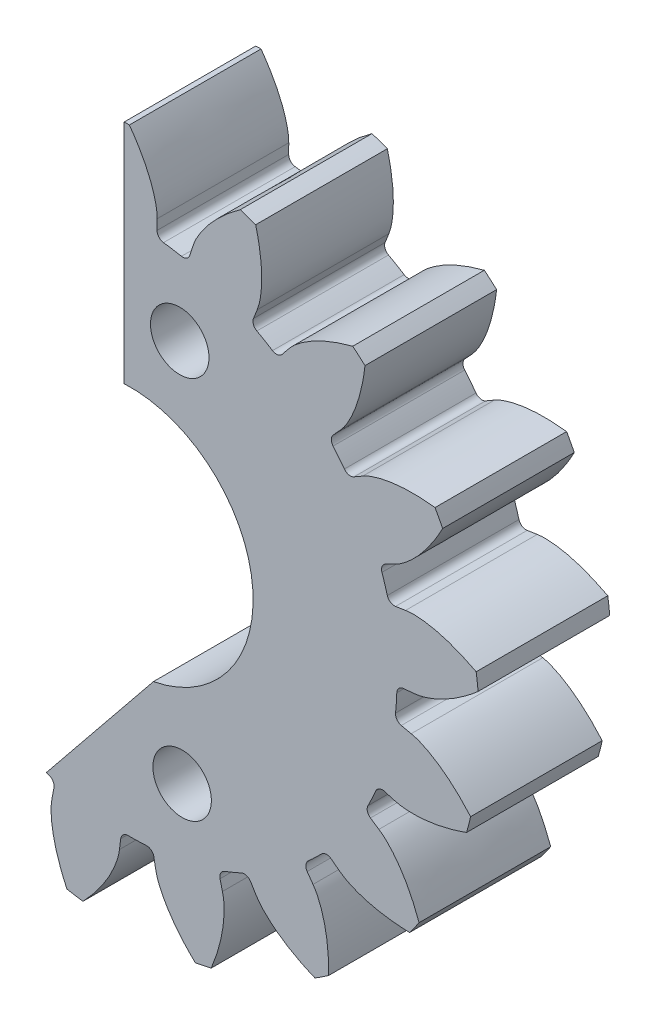
SolidWorks part; units mm, degrees
ref_plane "Front" through (0, 0, 0) normal (0, 0, 1) x (1, 0, 0)
ref_plane "Top" through (0, 0, 0) normal (0, 1, 0) x (1, 0, 0)
ref_plane "Right" through (0, 0, 0) normal (1, 0, 0) x (0, 0, -1)
sketch "Sketch1" plane through (0, 0, 0) normal (0, 0, 1) x (1, 0, 0)
  line L68 (2.1427, 9.4464) -> (2.0368, 9.1165)
  line L69 (0.916, 9.2963) -> (0.9185, 9.6427)
  line L70 (-1.4144, 9.5825) -> (-1.394, 9.2367)
  line L71 (-2.504, 8.9994) -> (-2.6268, 9.3234)
  line L72 (-4.7805, 8.4245) -> (-4.6366, 8.1093)
  line L73 (-5.5859, 7.4871) -> (-5.8174, 7.7449)
  line L74 (-7.501, 6.1287) -> (-7.2529, 5.8868)
  line L75 (-7.9134, 4.9637) -> (-8.2224, 5.1204)
  line L76 (-9.2084, 3.0052) -> (-8.8897, 2.8692)
  line L77 (-9.1721, 1.7699) -> (-9.5168, 1.8043)
  line L78 (-9.6722, -0.5242) -> (-9.3259, -0.5358)
  line L79 (-9.1921, -1.663) -> (-9.526, -1.7554)
  line L80 (-8.8296, -3.9828) -> (-8.5026, -3.8686)
  line L81 (-7.9706, -4.8713) -> (-8.2486, -5.078)
  line L82 (-6.7946, -6.9035) -> (-6.5309, -6.6788)
  line L83 (-5.6727, -7.4216) -> (-5.8572, -7.7148)
  line L84 (-3.842, -8.8918) -> (-3.6772, -8.587)
  line L85 (-2.6086, -8.9696) -> (-2.6747, -9.3097)
  line L86 (-0.3704, -9.6793) -> (-0.3269, -9.3356)
  line L87 (0.8078, -9.3063) -> (0.8689, -9.6473)
  line L88 (3.1511, -9.1595) -> (3.0675, -8.8232)
  line L89 (4.115, -8.3861) -> (4.2953, -8.6819)
  line L90 (6.2471, -7.4026) -> (6.0477, -7.1193)
  line L91 (6.8665, -6.3332) -> (7.1415, -6.544)
  line L92 (8.4994, -4.646) -> (8.2111, -4.4539)
  line L93 (8.6907, -3.4251) -> (9.0232, -3.5223)
  line L94 (9.6038, -1.2619) -> (9.2656, -1.1869)
  line L95 (9.3411, -0.0544) -> (9.6863, -0.0249)
  line L96 (9.4111, 2.2926) -> (9.0686, 2.2404)
  line L97 (8.73, 3.3237) -> (9.0412, 3.4759)
  line L98 (7.9475, 5.5374) -> (7.6469, 5.365)
  line L99 (6.9398, 6.2529) -> (7.1751, 6.5072)
  line L100 (5.4104, 8.0345) -> (5.1925, 7.7651)
  line L101 (4.2123, 8.3376) -> (4.3399, 8.6597)
  circle A0 centre (0, 0) radius 1.5
  arc A136 (4.2867, 11.1494) -> (3.764, 11.3366) centre (0, 0) ccw
  arc A137 (1.7491, 8.9466) -> (2.0368, 9.1165) centre (1.7973, 9.1934) ccw
  arc A138 (1.7491, 8.9466) -> (1.1361, 9.0449) centre (0, 0) ccw
  arc A139 (0.916, 9.2963) -> (1.1361, 9.0449) centre (1.1675, 9.2944) ccw
  arc A140 (-0.0304, 11.945) -> (-0.5854, 11.9307) centre (0, 0) ccw
  arc A141 (-1.6009, 8.9743) -> (-1.394, 9.2367) centre (-1.6451, 9.2219) ccw
  arc A142 (-1.6009, 8.9743) -> (-2.208, 8.8445) centre (0, 0) ccw
  arc A143 (-2.504, 8.9994) -> (-2.208, 8.8445) centre (-2.2689, 9.0885) ccw
  arc A144 (-4.3434, 11.1274) -> (-4.8558, 10.9136) centre (0, 0) ccw
  arc A145 (-4.7347, 7.79) -> (-4.6366, 8.1093) centre (-4.8653, 8.0049) ccw
  arc A146 (-4.7347, 7.79) -> (-5.2539, 7.4497) centre (0, 0) ccw
  arc A147 (-5.5859, 7.4871) -> (-5.2539, 7.4497) centre (-5.3988, 7.6552) ccw
  arc A148 (-8.0698, 8.807) -> (-8.4703, 8.4225) centre (0, 0) ccw
  arc A149 (-7.229, 5.5536) -> (-7.2529, 5.8868) centre (-7.4285, 5.7068) ccw
  arc A150 (-7.229, 5.5536) -> (-7.5902, 5.0487) centre (0, 0) ccw
  arc A151 (-7.9134, 4.9637) -> (-7.5902, 5.0487) centre (-7.7996, 5.188) ccw
  arc A152 (-10.7063, 5.2971) -> (-10.9409, 4.7939) centre (0, 0) ccw
  arc A153 (-8.7471, 2.5671) -> (-8.8897, 2.8692) centre (-8.9884, 2.6379) ccw
  arc A154 (-8.7471, 2.5671) -> (-8.9015, 1.9659) centre (0, 0) ccw
  arc A155 (-9.1721, 1.7699) -> (-8.9015, 1.9659) centre (-9.147, 2.0201) ccw
  arc A156 (-11.8969, 1.0719) -> (-11.9338, 0.5179) centre (0, 0) ccw
  arc A157 (-9.0837, -0.766) -> (-9.3259, -0.5358) centre (-9.3343, -0.7872) ccw
  arc A158 (-9.0837, -0.766) -> (-9.0105, -1.3825) centre (0, 0) ccw
  arc A159 (-9.1921, -1.663) -> (-9.0105, -1.3825) centre (-9.2591, -1.4206) ccw
  arc A160 (-11.4807, -3.2982) -> (-11.3151, -3.8281) centre (0, 0) ccw
  arc A161 (-8.1936, -3.9957) -> (-8.5026, -3.8686) centre (-8.4196, -4.106) ccw
  arc A162 (-8.1936, -3.9957) -> (-7.9027, -4.5441) centre (0, 0) ccw
  arc A163 (-7.9706, -4.8713) -> (-7.9027, -4.5441) centre (-8.1207, -4.6695) ccw
  arc A164 (-9.514, -7.2228) -> (-9.1681, -7.6571) centre (0, 0) ccw
  arc A165 (-6.1969, -6.6858) -> (-6.5309, -6.6788) centre (-6.3678, -6.8702) ccw
  arc A166 (-6.1969, -6.6858) -> (-5.7275, -7.092) centre (0, 0) ccw
  arc A167 (-5.6727, -7.4216) -> (-5.7275, -7.092) centre (-5.8855, -7.2877) ccw
  arc A168 (-6.2624, -10.1719) -> (-5.783, -10.4519) centre (0, 0) ccw
  arc A169 (-3.3632, -8.4729) -> (-3.6772, -8.587) centre (-3.456, -8.7066) ccw
  arc A170 (-3.3632, -8.4729) -> (-2.7788, -8.6821) centre (0, 0) ccw
  arc A171 (-2.6086, -8.9696) -> (-2.7788, -8.6821) centre (-2.8554, -8.9216) ccw
  arc A172 (-2.165, -11.7472) -> (-1.6168, -11.8352) centre (0, 0) ccw
  arc A173 (-0.0754, -9.1157) -> (-0.3269, -9.3356) centre (-0.0774, -9.3671) ccw
  arc A174 (-0.0754, -9.1157) -> (0.5452, -9.0997) centre (0, 0) ccw
  arc A175 (0.8078, -9.3063) -> (0.5452, -9.0997) centre (0.5602, -9.3507) ccw
  arc A176 (2.2248, -11.7361) -> (2.7677, -11.62) centre (0, 0) ccw
  arc A177 (3.2227, -8.5273) -> (3.0675, -8.8232) centre (3.3116, -8.7626) ccw
  arc A178 (3.2227, -8.5273) -> (3.7956, -8.2882) centre (0, 0) ccw
  arc A179 (4.115, -8.3861) -> (3.7956, -8.2882) centre (3.9003, -8.5169) ccw
  arc A180 (6.3141, -10.1399) -> (6.7785, -9.8355) centre (0, 0) ccw
  arc A181 (6.0855, -6.7873) -> (6.0477, -7.1193) centre (6.2534, -6.9746) ccw
  arc A182 (6.0855, -6.7873) -> (6.5333, -6.3574) centre (0, 0) ccw
  arc A183 (6.8665, -6.3332) -> (6.5333, -6.3574) centre (6.7135, -6.5328) ccw
  arc A184 (9.5507, -7.1742) -> (9.8737, -6.7227) centre (0, 0) ccw
  arc A185 (8.1264, -4.1307) -> (8.2111, -4.4539) centre (8.3506, -4.2446) ccw
  arc A186 (8.1264, -4.1307) -> (8.3887, -3.568) centre (0, 0) ccw
  arc A187 (8.6907, -3.4251) -> (8.3887, -3.568) centre (8.6201, -3.6665) ccw
  arc A188 (11.4974, -3.2397) -> (11.6355, -2.7019) centre (0, 0) ccw
  arc A189 (9.0698, -0.9161) -> (9.2656, -1.1869) centre (9.32, -0.9414) ccw
  arc A190 (9.0698, -0.9161) -> (9.1112, -0.2967) centre (0, 0) ccw
  arc A191 (9.3411, -0.0544) -> (9.1112, -0.2967) centre (9.3625, -0.3049) ccw
  arc A192 (11.8913, 1.1324) -> (11.8258, 1.6838) centre (0, 0) ccw
  arc A193 (8.7883, 2.4221) -> (9.0686, 2.2404) centre (9.0307, 2.489) ccw
  arc A194 (8.7883, 2.4221) -> (8.6031, 3.0146) centre (0, 0) ccw
  arc A195 (8.73, 3.3237) -> (8.6031, 3.0146) centre (8.8404, 3.0978) ccw
  arc A196 (10.6792, 5.3516) -> (10.419, 5.842) centre (0, 0) ccw
  arc A197 (7.3199, 5.4333) -> (7.6469, 5.365) centre (7.5218, 5.5832) ccw
  arc A198 (7.3199, 5.4333) -> (6.9331, 5.9189) centre (0, 0) ccw
  arc A199 (6.9398, 6.2529) -> (6.9331, 5.9189) centre (7.1244, 6.0821) ccw
  arc A200 (8.0248, 8.848) -> (7.605, 9.2113) centre (0, 0) ccw
  arc A201 (4.8629, 7.7106) -> (5.1925, 7.7651) centre (4.997, 7.9233) ccw
  arc A202 (4.8629, 7.7106) -> (4.3268, 8.0237) centre (0, 0) ccw
  arc A203 (4.2123, 8.3376) -> (4.3268, 8.0237) centre (4.4462, 8.245) ccw
  spline S68 degree 3 poles (3.764, 11.3366) (3.2587, 10.9714) (2.6231, 10.3935) (2.2067, 9.6531) (2.1427, 9.4464) knots -0.008485 -0.008485 -0.008485 -0.008485 0.741457 1 1 1 1
  spline S69 degree 3 poles (0.9185, 9.6427) (0.9201, 9.8535) (0.7567, 10.6863) (0.3366, 11.435) (-0.0304, 11.945) knots 0 0 0 0 0.250058 1 1 1 1
  spline S70 degree 3 poles (-0.5854, 11.9307) (-0.9247, 11.4077) (-1.3085, 10.6392) (-1.4294, 9.7984) (-1.4144, 9.5825) knots -0.008485 -0.008485 -0.008485 -0.008485 0.741457 1 1 1 1
  spline S71 degree 3 poles (-2.6268, 9.3234) (-2.7015, 9.5204) (-3.1547, 10.238) (-3.8169, 10.7844) (-4.3434, 11.1274) knots 0 0 0 0 0.250058 1 1 1 1
  spline S72 degree 3 poles (-4.8558, 10.9136) (-4.9832, 10.3033) (-5.0635, 9.4481) (-4.8725, 8.6204) (-4.7805, 8.4245) knots -0.008485 -0.008485 -0.008485 -0.008485 0.741457 1 1 1 1
  spline S73 degree 3 poles (-5.8174, 7.7449) (-5.9583, 7.9016) (-6.64, 8.4071) (-7.455, 8.6773) (-8.0698, 8.807) knots 0 0 0 0 0.250058 1 1 1 1
  spline S74 degree 3 poles (-8.4703, 8.4225) (-8.3687, 7.8074) (-8.1346, 6.9809) (-7.6575, 6.2781) (-7.501, 6.1287) knots -0.008485 -0.008485 -0.008485 -0.008485 0.741457 1 1 1 1
  spline S75 degree 3 poles (-8.2224, 5.1204) (-8.4103, 5.2157) (-9.2286, 5.4407) (-10.0862, 5.3983) (-10.7063, 5.2971) knots 0 0 0 0 0.250058 1 1 1 1
  spline S76 degree 3 poles (-10.9409, 4.7939) (-10.624, 4.2571) (-10.1071, 3.5709) (-9.4083, 3.088) (-9.2084, 3.0052) knots -0.008485 -0.008485 -0.008485 -0.008485 0.741457 1 1 1 1
  spline S77 degree 3 poles (-9.5168, 1.8043) (-9.7265, 1.8253) (-10.5708, 1.7395) (-11.3552, 1.3902) (-11.8969, 1.0719) knots 0 0 0 0 0.250058 1 1 1 1
  spline S78 degree 3 poles (-11.9338, 0.5179) (-11.4444, 0.1318) (-10.7145, -0.3213) (-9.8885, -0.5192) (-9.6722, -0.5242) knots -0.008485 -0.008485 -0.008485 -0.008485 0.741457 1 1 1 1
  spline S79 degree 3 poles (-9.526, -1.7554) (-9.7291, -1.8116) (-10.4854, -2.1966) (-11.0906, -2.8056) (-11.4807, -3.2982) knots 0 0 0 0 0.250058 1 1 1 1
  spline S80 degree 3 poles (-11.3151, -3.8281) (-10.7192, -4.0113) (-9.875, -4.1701) (-9.0332, -4.0563) (-8.8296, -3.9828) knots -0.008485 -0.008485 -0.008485 -0.008485 0.741457 1 1 1 1
  spline S81 degree 3 poles (-8.2486, -5.078) (-8.4177, -5.2038) (-8.9839, -5.836) (-9.3281, -6.6225) (-9.514, -7.2228) knots 0 0 0 0 0.250058 1 1 1 1
  spline S82 degree 3 poles (-9.1681, -7.6571) (-8.5463, -7.6126) (-7.7017, -7.4558) (-6.9579, -7.0456) (-6.7946, -6.9035) knots -0.008485 -0.008485 -0.008485 -0.008485 0.741457 1 1 1 1
  spline S83 degree 3 poles (-5.8572, -7.7148) (-5.9694, -7.8932) (-6.269, -8.6873) (-6.3059, -9.545) (-6.2624, -10.1719) knots 0 0 0 0 0.250058 1 1 1 1
  spline S84 degree 3 poles (-5.783, -10.4519) (-5.2192, -10.1859) (-4.4883, -9.7345) (-3.9429, -9.0833) (-3.842, -8.8918) knots -0.008485 -0.008485 -0.008485 -0.008485 0.741457 1 1 1 1
  spline S85 degree 3 poles (-2.6747, -9.3097) (-2.715, -9.5166) (-2.7074, -10.3653) (-2.432, -11.1784) (-2.165, -11.7472) knots 0 0 0 0 0.250058 1 1 1 1
  spline S86 degree 3 poles (-1.6168, -11.8352) (-1.1872, -11.3834) (-0.6687, -10.6985) (-0.3954, -9.8942) (-0.3704, -9.6793) knots -0.008485 -0.008485 -0.008485 -0.008485 0.741457 1 1 1 1
  spline S87 degree 3 poles (0.8689, -9.6473) (0.9062, -9.8547) (1.2197, -10.6434) (1.7703, -11.3021) (2.2248, -11.7361) knots 0 0 0 0 0.250058 1 1 1 1
  spline S88 degree 3 poles (2.7677, -11.62) (3.0051, -11.0436) (3.2412, -10.2176) (3.2055, -9.3689) (3.1511, -9.1595) knots -0.008485 -0.008485 -0.008485 -0.008485 0.741457 1 1 1 1
  spline S89 degree 3 poles (4.2953, -8.6819) (4.4049, -8.8619) (4.9822, -9.484) (5.7336, -9.8994) (6.3141, -10.1399) knots 0 0 0 0 0.250058 1 1 1 1
  spline S90 degree 3 poles (6.7785, -9.8355) (6.7916, -9.2122) (6.7134, -8.3568) (6.3735, -7.5783) (6.2471, -7.4026) knots -0.008485 -0.008485 -0.008485 -0.008485 0.741457 1 1 1 1
  spline S91 degree 3 poles (7.1415, -6.544) (7.3088, -6.6723) (8.0718, -7.0438) (8.9225, -7.1597) (9.5507, -7.1742) knots 0 0 0 0 0.250058 1 1 1 1
  spline S92 degree 3 poles (9.8737, -6.7227) (9.6608, -6.1367) (9.2788, -5.3673) (8.6807, -4.7642) (8.4994, -4.646) knots -0.008485 -0.008485 -0.008485 -0.008485 0.741457 1 1 1 1
  spline S93 degree 3 poles (9.0232, -3.5223) (9.2255, -3.5815) (10.0712, -3.6523) (10.9064, -3.4531) (11.4974, -3.2397) knots 0 0 0 0 0.250058 1 1 1 1
  spline S94 degree 3 poles (11.6355, -2.7019) (11.2253, -2.2324) (10.5911, -1.653) (9.8155, -1.3066) (9.6038, -1.2619) knots -0.008485 -0.008485 -0.008485 -0.008485 0.741457 1 1 1 1
  spline S95 degree 3 poles (9.6863, -0.0249) (9.8963, -0.007) (10.7105, 0.2325) (11.4173, 0.7199) (11.8913, 1.1324) knots 0 0 0 0 0.250058 1 1 1 1
  spline S96 degree 3 poles (11.8258, 1.6838) (11.2737, 1.9734) (10.4731, 2.2846) (9.6247, 2.3274) (9.4111, 2.2926) knots -0.008485 -0.008485 -0.008485 -0.008485 0.741457 1 1 1 1
  spline S97 degree 3 poles (9.0412, 3.4759) (9.2306, 3.5684) (9.9033, 4.0859) (10.3862, 4.7957) (10.6792, 5.3516) knots 0 0 0 0 0.250058 1 1 1 1
  spline S98 degree 3 poles (10.419, 5.842) (9.7996, 5.9126) (8.9406, 5.9136) (8.134, 5.6471) (7.9475, 5.5374) knots -0.008485 -0.008485 -0.008485 -0.008485 0.741457 1 1 1 1
  spline S99 degree 3 poles (7.1751, 6.5072) (7.3182, 6.6619) (7.7585, 7.3874) (7.9524, 8.2238) (8.0248, 8.848) knots 0 0 0 0 0.250058 1 1 1 1
  spline S100 degree 3 poles (7.605, 9.2113) (7.002, 9.0534) (6.2006, 8.744) (5.5448, 8.2041) (5.4104, 8.0345) knots -0.008485 -0.008485 -0.008485 -0.008485 0.741457 1 1 1 1
  spline S101 degree 3 poles (4.3399, 8.6597) (4.4174, 8.8557) (4.566, 9.6913) (4.4446, 10.5412) (4.2867, 11.1494) knots 0 0 0 0 0.250058 1 1 1 1
  dimension "D1" = 3
extrude "Boss-Extrude1" add sketch "Sketch1" along normal blind 4.5
sketch "Sketch3" plane through (0, 0, 4.5) normal (0, 0, 1) x (1, 0, 0)
  line L0 (0, 0) -> (-24.6444, 0)
sketch "Sketch4" plane through (0, 0, 0) normal (0, 0, -1) x (-1, 0, 0)
  line L0 (12.8632, 15.1898) -> (0.2099, 15.1898)
  line L1 (3.0728, -8.5825) -> (3.0728, -14.2917) construction
  line L2 (3.0728, -14.2917) -> (12.6632, -14.2917) construction
  line L4 (3.0728, -8.5825) -> (-0.6826, -3.9413) construction
  line L5 (12.6632, -14.2917) -> (12.6632, 14.9898) construction
  line L6 (12.6632, 14.9898) -> (0.4099, 14.9898) construction
  line L7 (0.2099, 15.1898) -> (0.2099, 4.1947)
  line L8 (2.8728, -8.6533) -> (-0.7915, -4.1248)
  line L9 (2.8728, -8.6533) -> (2.8728, -14.4917)
  line L10 (2.8728, -14.4917) -> (12.8632, -14.4917)
  line L11 (12.8632, -14.4917) -> (12.8632, 15.1898)
  line L22 (0.4099, 14.9898) -> (0.4099, 3.9789) construction
  arc A0 (0.2099, 4.1947) -> (-0.7915, -4.1248) centre (0, 0) ccw
  arc A3 (0.4099, 3.9789) -> (-0.6826, -3.9413) centre (0, 0) ccw construction
  dimension "D1" = 0.2
extrude "Cut-Extrude1" cut sketch "Sketch4" against normal through all
sketch "Sketch5" plane through (0, 0, 4.5) normal (0, 0, 1) x (1, 0, 0)
  line L1 (-0.2099, 11.9432) -> (-0.2099, 4.1947) construction
  circle A2 centre (1.6901, 6.4124) radius 1
  circle A3 centre (1.7728, -6.6584) radius 1
  dimension "D1" = 2
  dimension "D2" = 1.9
extrude "Cut-Extrude2" cut sketch "Sketch5" against normal through all
